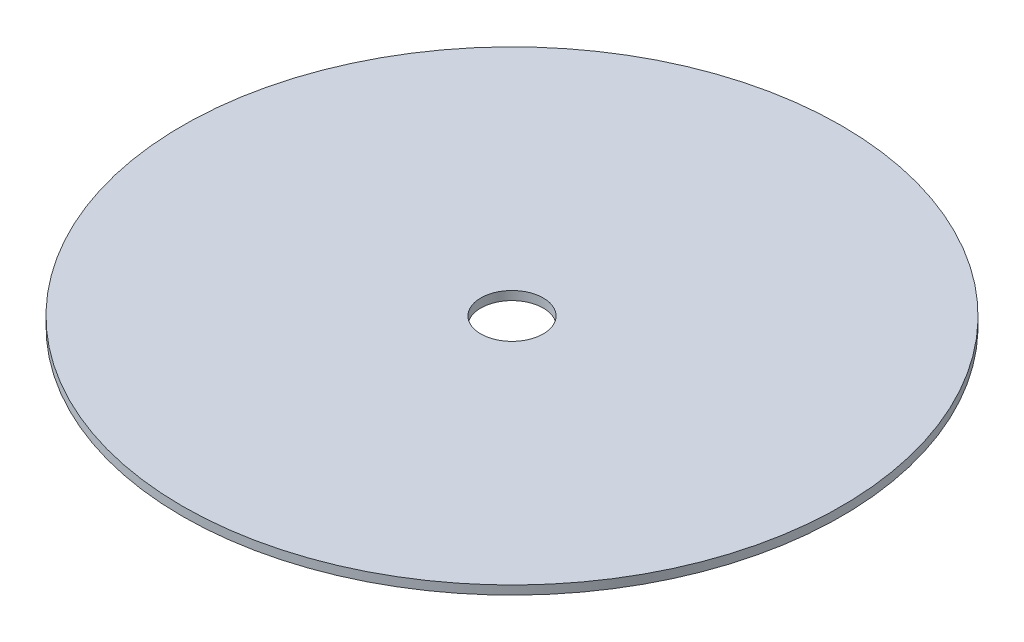
SolidWorks part; units mm, degrees
ref_plane "Front Plane" through (0, 0, 0) normal (0, 0, 1) x (1, 0, 0)
ref_plane "Top Plane" through (0, 0, 0) normal (0, 1, 0) x (1, 0, 0)
ref_plane "Right Plane" through (0, 0, 0) normal (1, 0, 0) x (0, 0, -1)
sketch "Sketch1" plane through (0, 0, 0) normal (0, 1, 0) x (1, 0, 0)
  circle A0 centre (0, 0) radius 150
  dimension "D1" = 300
extrude "Boss-Extrude1" add sketch "Sketch1" along normal blind 4
sketch "Sketch2" plane through (0, 0, 0) normal (0, -1, 0) x (1, 0, 0)
  circle A0 centre (0, 0) radius 14.2
  dimension "D1" = 28.4
extrude "Cut-Extrude1" cut sketch "Sketch2" against normal blind 10
